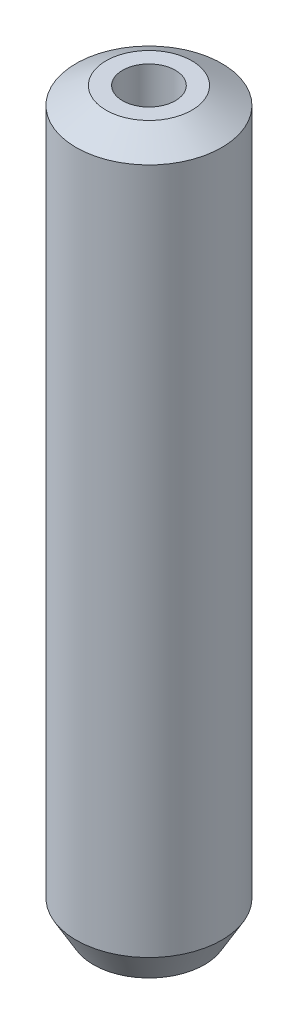
SolidWorks part; units mm, degrees
ref_plane "Front Plane" through (0, 0, 0) normal (0, 0, 1) x (1, 0, 0)
ref_plane "Top Plane" through (0, 0, 0) normal (0, 1, 0) x (1, 0, 0)
ref_plane "Right Plane" through (0, 0, 0) normal (1, 0, 0) x (0, 0, -1)
sketch "Sketch1" plane through (0, 0, 0) normal (0, 1, 0) x (1, 0, 0)
  circle A0 centre (0, 0) radius 22.5
  dimension "SHAFT_OD" = 45
extrude "Boss-Extrude1" add sketch "Sketch1" along normal blind 226.604
sketch "Sketch2" plane through (0, 0, 0) normal (0, 1, 0) x (1, 0, 0)
  circle A0 centre (0, 0) radius 8.1599
  dimension "BORE_D" = 16.3197
extrude "Cut-Extrude1" cut sketch "Sketch2" along normal through all
chamfer "Chamfer1" distance 5.3455 angle 60 2 edges at (0, 226.604, 22.5) (0, 0, 22.5) first distance on face at (0, 226.604, 22.5) first distance on face at (0, 0, 8.1599)
